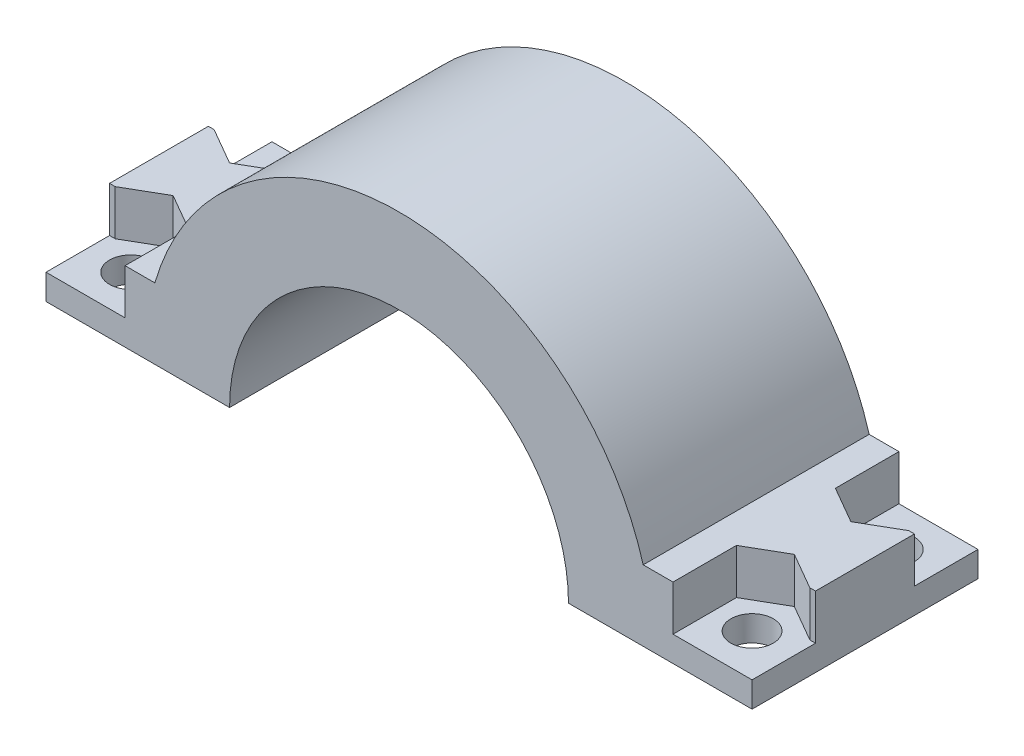
SolidWorks part; units mm, degrees
ref_plane "Front Plane" through (0, 0, 0) normal (0, 0, 1) x (1, 0, 0)
ref_plane "Top Plane" through (0, 0, 0) normal (0, 1, 0) x (1, 0, 0)
ref_plane "Right Plane" through (0, 0, 0) normal (1, 0, 0) x (0, 0, -1)
sketch "Sketch7" plane through (0, 0, 0) normal (0, 0, 1) x (1, 0, 0)
  line L17 (28.8688, -27.166) -> (28.8688, -22.166)
  line L20 (-21.1312, -22.166) -> (-21.1312, -27.166)
  line L24 (-21.1312, -27.166) -> (-8.1312, -27.166)
  line L25 (15.8688, -27.166) -> (28.8688, -27.166)
  line L28 (-13.4228, -22.166) -> (-21.1312, -22.166)
  line L29 (21.1604, -22.166) -> (28.8688, -22.166)
  arc A5 (-8.1312, -27.166) -> (15.8688, -27.166) centre (3.8688, -27.166) cw
  arc A6 (21.1604, -22.166) -> (-13.4228, -22.166) centre (3.8688, -27.166) ccw
  dimension "D4" = 50
  dimension "D2" = 12
  dimension "D7" = 5
  dimension "D8" = 5
extrude "Boss-Extrude1" add sketch "Sketch7" along normal blind 16
sketch "Sketch13" plane through (0, 0, 0) normal (0, 1, 0) x (1, 0, 0)
  line L0 (-15.5331, -4.5) -> (-15.5331, -1.5)
  line L1 (-20.7293, -4.5) -> (-18.1312, -6)
  line L2 (-18.1312, -6) -> (-15.5331, -4.5)
  line L3 (-21.1312, -11.5) -> (-20.7293, -11.5)
  line L4 (-20.7293, 0) -> (-18.1312, 0)
  line L5 (-18.1312, 0) -> (-15.5331, 0)
  line L6 (-15.5331, 0) -> (-15.5331, -1.5)
  line L7 (-20.7293, 0) -> (-21.1312, 0)
  line L8 (-21.1312, 0) -> (-21.1312, -4.5)
  line L9 (-21.1312, -4.5) -> (-20.7293, -4.5)
  line L10 (-15.5331, -11.5) -> (-15.5331, -11.5448)
  line L11 (-21.1312, -16) -> (-21.1312, -11.5)
  line L12 (-20.7293, -16) -> (-21.1312, -16)
  line L13 (-15.5331, -16) -> (-15.5331, -11.5448)
  line L14 (-18.1312, -16) -> (-15.5331, -16)
  line L15 (-20.7293, -16) -> (-18.1312, -16)
  line L16 (-18.1312, -10) -> (-15.5331, -11.5)
  line L17 (-20.7293, -11.5) -> (-18.1312, -10)
  line L18 (23.2707, -4.5) -> (23.2707, -1.5)
  line L19 (28.4669, -11.5065) -> (25.8688, -10.0065)
  line L20 (25.8688, -10.0065) -> (23.2707, -11.5065)
  line L21 (28.4669, -16.0065) -> (25.8688, -16.0065)
  line L22 (25.8688, -16.0065) -> (23.2707, -16.0065)
  line L23 (23.2707, -16.0065) -> (23.2707, -14.5065)
  line L24 (28.4669, -16.0065) -> (28.8688, -16.0065)
  line L25 (28.8688, -16.0065) -> (28.8688, -11.5065)
  line L26 (23.2707, -11.5065) -> (23.2707, -14.5065)
  line L27 (28.8688, -4.5) -> (28.4669, -4.5)
  line L28 (28.8688, 0) -> (28.8688, -4.5)
  line L29 (28.4669, 0) -> (28.8688, 0)
  line L30 (23.2707, 0) -> (23.2707, -1.5)
  line L31 (25.8688, 0) -> (23.2707, 0)
  line L32 (28.4669, 0) -> (25.8688, 0)
  line L33 (28.8688, -11.5065) -> (28.4669, -11.5065)
  line L34 (25.8688, -6) -> (23.2707, -4.5)
  line L35 (28.4669, -4.5) -> (25.8688, -6)
  line L36 (-21.1312, -16) -> (-21.1312, 0) construction
  line L37 (-13.4228, -16) -> (-21.1312, -16) construction
  line L38 (-13.4228, 0) -> (-21.1312, 0) construction
  line L39 (28.8688, -16) -> (28.8688, 0) construction
  line L40 (28.8688, 0) -> (21.1604, 0) construction
  line L41 (28.8688, -16) -> (21.1604, -16) construction
  arc A0 (-19.4302, -5.25) -> (-15.5331, -3) centre (-18.1312, -3) ccw construction
  arc A1 (-19.4302, -10.75) -> (-20.5427, -12.0333) centre (-18.1312, -13) cw construction
  arc A2 (27.1678, -10.75) -> (23.2707, -13) centre (25.8688, -13) ccw construction
  arc A3 (27.1678, -5.25) -> (23.2707, -3) centre (25.8688, -3) cw construction
  dimension "D1" = 3
  dimension "D2" = 2.5981
  dimension "D3" = 2.5981
  dimension "D4" = 3
  dimension "D5" = 3
  dimension "D6" = 3
  dimension "D7" = 3
  dimension "D8" = 3
  dimension "D9" = 3
  dimension "D10" = 3
  dimension "D11" = 3
  dimension "D12" = 0
  dimension "D13" = 0
  dimension "D14" = 0
extrude "Cut-Extrude12" cut sketch "Sketch13" against normal blind 3.2 from surface starting at face at (25.0146, -22.166, 8)
sketch "Sketch14" plane through (0, 0, 0) normal (0, 1, 0) x (1, 0, 0)
  line L0 (-21.1312, 0) -> (-15.5331, 0) construction
  line L1 (-21.1312, -4.5) -> (-21.1312, 0) construction
  line L2 (-21.1312, -16) -> (-21.1312, -11.5) construction
  line L3 (-15.5331, -16) -> (-21.1312, -16) construction
  line L4 (28.8688, 0) -> (28.8688, -4.5) construction
  line L5 (23.2707, 0) -> (28.8688, 0) construction
  line L6 (23.2707, -16) -> (28.8688, -16) construction
  line L7 (28.8688, -11.5065) -> (28.8688, -16) construction
  circle A0 centre (-18.1312, -3) radius 1.5
  circle A1 centre (-18.1312, -13) radius 1.5
  circle A2 centre (25.8688, -3) radius 1.5
  circle A3 centre (25.8688, -13) radius 1.5
  dimension "D1" = 3
  dimension "D2" = 3
  dimension "D3" = 3
  dimension "D4" = 3
  dimension "D5" = 3
  dimension "D6" = 3
  dimension "D7" = 3
  dimension "D8" = 3
extrude "Cut-Extrude13" cut sketch "Sketch14" against normal blind 50
